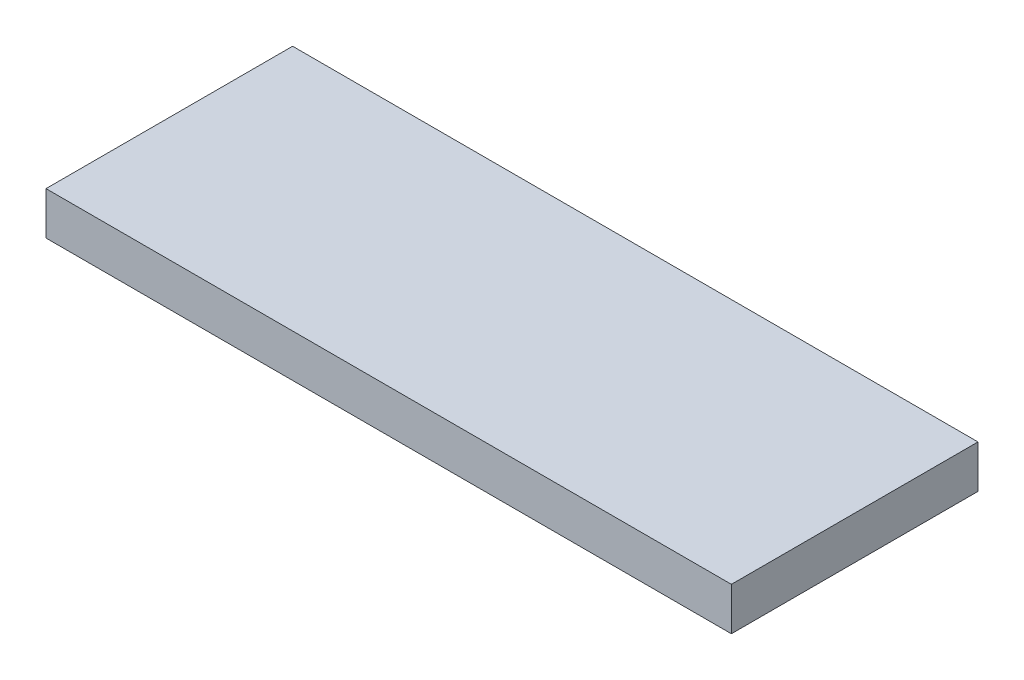
SolidWorks part; units mm, degrees
ref_plane "Front Plane" through (0, 0, 0) normal (0, 0, 1) x (1, 0, 0)
ref_plane "Top Plane" through (0, 0, 0) normal (0, 1, 0) x (1, 0, 0)
ref_plane "Right Plane" through (0, 0, 0) normal (1, 0, 0) x (0, 0, -1)
sketch "Sketch1" plane through (0, 0, 0) normal (0, 1, 0) x (1, 0, 0)
  line L1 (-35.3879, -3.6558) -> (-15.0679, -3.6558)
  line L2 (-35.3879, -3.6558) -> (-35.3879, 3.6558)
  line L3 (-35.3879, 3.6558) -> (-15.0679, 3.6558)
  line L4 (-15.0679, -3.6558) -> (-15.0679, 3.6558)
  line L5 (-35.3879, -3.6558) -> (-15.0679, 3.6558) construction
  line L6 (-35.3879, 3.6558) -> (-15.0679, -3.6558) construction
  point P0 (-25.2279, 0)
  dimension "D1" = 20.32
  dimension "D2" = 7.3115
extrude "Boss-Extrude1" add sketch "Sketch1" along normal blind 1.27 contours L3 L4 L1 L2
ref_axis "Axis1" through (-15.0679, 0, 0) along (-1, 0, 0)
